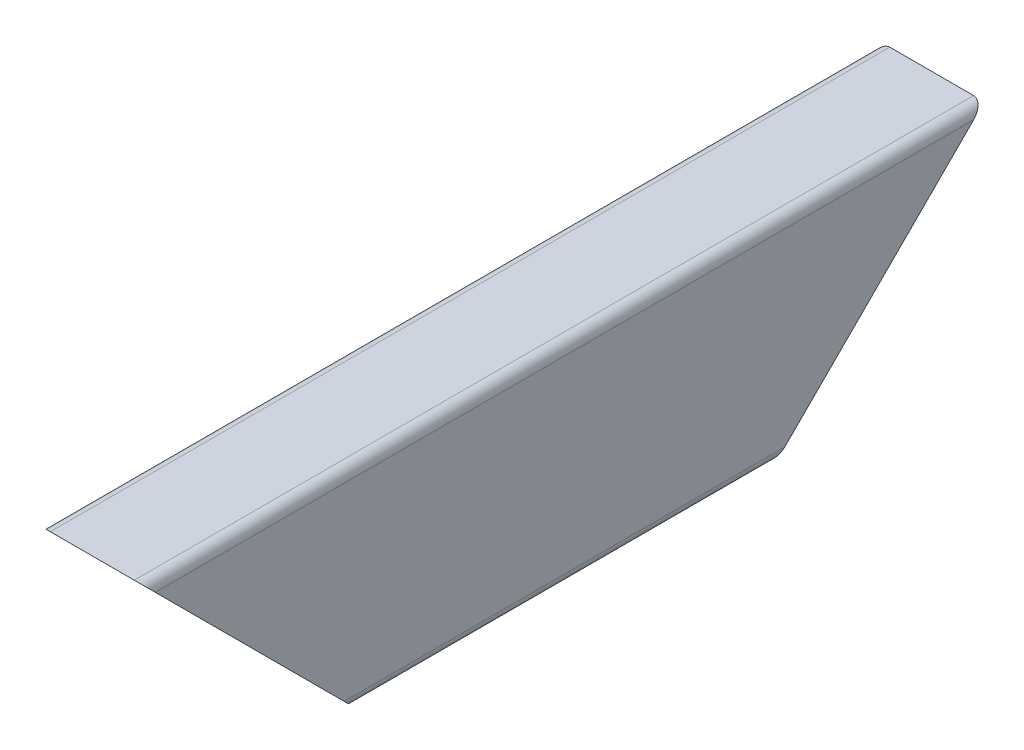
SolidWorks part; units mm, degrees
material "6061-T6 (SS)"
ref_plane "Front" through (0, 0, 0) normal (0, 0, 1) x (1, 0, 0)
ref_plane "Top" through (0, 0, 0) normal (0, 1, 0) x (1, 0, 0)
ref_plane "Right" through (0, 0, 0) normal (1, 0, 0) x (0, 0, -1)
sketch "Sketch1" plane through (0, 0, 0) normal (0, 0, 1) x (1, 0, 0)
  line L1 (-10.16, -25.4) -> (10.16, -25.4)
  line L2 (-12.7, -22.86) -> (-12.7, 22.86)
  line L3 (-10.16, 25.4) -> (10.16, 25.4)
  line L4 (12.7, -22.86) -> (12.7, 22.86)
  line L5 (-12.7, -25.4) -> (12.7, 25.4) construction
  line L6 (-12.7, 25.4) -> (12.7, -25.4) construction
  arc A0 (-10.16, -25.4) -> (-12.7, -22.86) centre (-10.16, -22.86) cw
  arc A1 (10.16, -25.4) -> (12.7, -22.86) centre (10.16, -22.86) ccw
  arc A2 (10.16, 25.4) -> (12.7, 22.86) centre (10.16, 22.86) cw
  arc A3 (-12.7, 22.86) -> (-10.16, 25.4) centre (-10.16, 22.86) cw
  point P0 (0, 0)
  dimension "D3" = 2.54
  dimension "D1" = 25.4
  dimension "D2" = 50.8
extrude "Extrude-Thin1" add sketch "Sketch1" along normal blind 203.2 thin thin type one direction reverse wall 1.5875
sketch "Sketch2" plane through (12.7, 0, 0) normal (1, 0, 0) x (0, 0, -1)
  line L0 (-203.2, 25.4) -> (-152.4, -25.4)
  line L1 (-203.2, -25.4) -> (0, -25.4) construction
  line L2 (-152.4, -25.4) -> (-203.2, -25.4)
  line L3 (-203.2, -25.4) -> (-203.2, 25.4)
  line L4 (0, 25.4) -> (-50.8, -25.4)
  line L5 (-50.8, -25.4) -> (0, -25.4)
  line L6 (0, -25.4) -> (0, 25.4)
  dimension "D1" = 45
  dimension "D2" = 45
extrude "Cut-Extrude1" cut sketch "Sketch2" against normal through all
